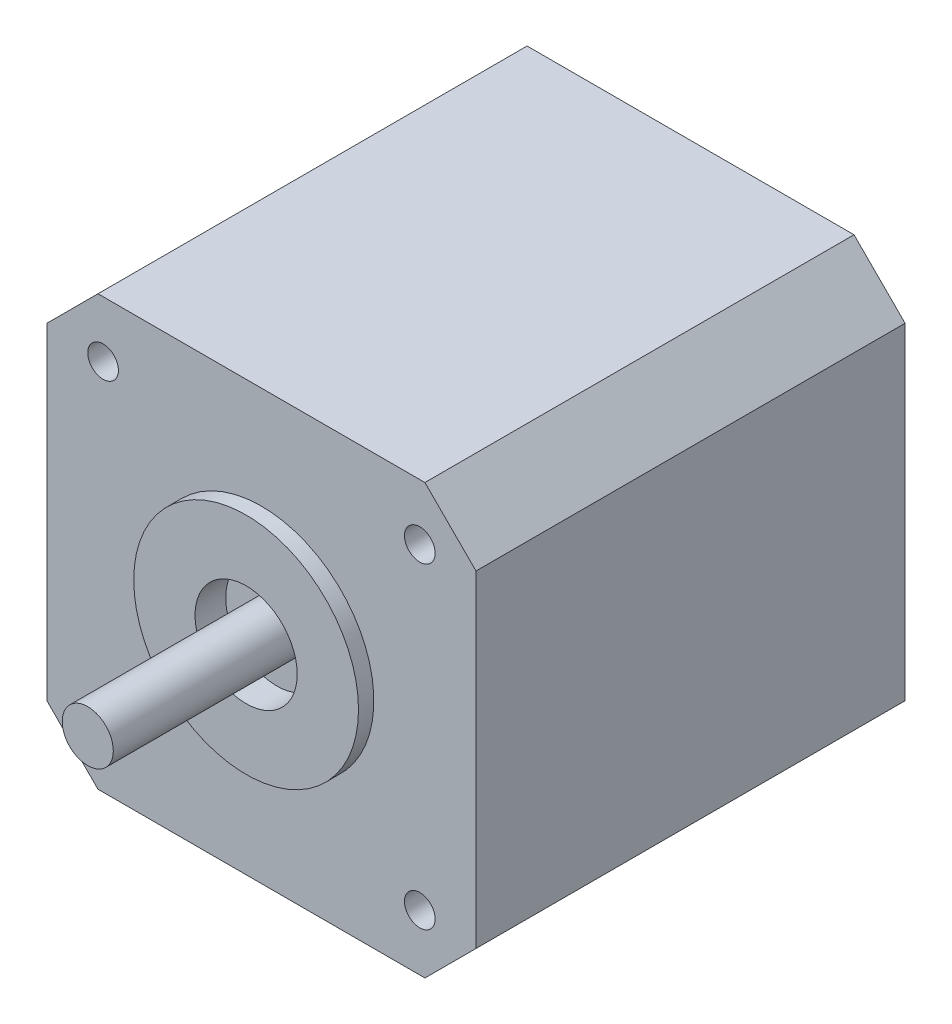
SolidWorks part; units mm, degrees
ref_plane "Front Plane" through (0, 0, 0) normal (0, 0, 1) x (1, 0, 0)
ref_plane "Top Plane" through (0, 0, 0) normal (0, 1, 0) x (1, 0, 0)
ref_plane "Right Plane" through (0, 0, 0) normal (1, 0, 0) x (0, 0, -1)
sketch "Sketch1" plane through (0, 0, 0) normal (0, 1, 0) x (1, 0, 0)
  line L1 (-21, -21) -> (21, -21)
  line L2 (-21, -21) -> (-21, 21)
  line L3 (-21, 21) -> (21, 21)
  line L4 (21, -21) -> (21, 21)
  line L5 (-21, -21) -> (21, 21) construction
  line L6 (-21, 21) -> (21, -21) construction
  point P0 (0, 0)
  dimension "D1" = 42
extrude "Boss-Extrude1" add sketch "Sketch1" along normal blind 42
sketch "Sketch2" plane through (0, 0, 21) normal (0, 0, 1) x (1, 0, 0)
  line L0 (0, 42) -> (0, 0) construction
  line L1 (-21, 42) -> (21, 42) construction
  line L2 (0, 21) -> (-21, 21) construction
  line L3 (-21, 42) -> (-21, 0) construction
  line L4 (21, 42) -> (21, 0) construction
  circle A0 centre (15.5, 36.5) radius 1.5
  circle A1 centre (-15.5, 36.5) radius 1.5
  circle A2 centre (15.5, 5.5) radius 1.5
  circle A3 centre (-15.5, 5.5) radius 1.5
  dimension "D1" = 3
  dimension "D2" = 5.5
  dimension "D3" = 5.5
extrude "Cut-Extrude1" cut sketch "Sketch2" against normal blind 42
sketch "Sketch3" plane through (0, 0, 21) normal (0, 0, 1) x (1, 0, 0)
  circle A0 centre (0, 21) radius 11
  dimension "D1" = 22
extrude "Boss-Extrude2" add sketch "Sketch3" along normal blind 1.5
sketch "Sketch4" plane through (0, 0, 22.5) normal (0, 0, 1) x (1, 0, 0)
  circle A0 centre (0, 21) radius 5
  dimension "D1" = 10
extrude "Cut-Extrude2" cut sketch "Sketch4" against normal blind 3
sketch "Sketch5" plane through (0, 0, 19.5) normal (0, 0, 1) x (1, 0, 0)
  circle A0 centre (0, 21) radius 2.5
  dimension "D1" = 5
extrude "Boss-Extrude3" add sketch "Sketch5" along normal blind 18.5
sketch "Sketch6" plane through (0, 0, -21) normal (0, 0, -1) x (-1, 0, 0)
  line L0 (0, 0) -> (0, 21) construction
  line L1 (-21, 0) -> (21, 0) construction
  line L2 (0, 21) -> (21, 21) construction
  line L3 (21, 42) -> (21, 0) construction
  circle A0 centre (15.5, 5.5) radius 3
  circle A1 centre (15.5, 36.5) radius 3
  circle A2 centre (-15.5, 5.5) radius 3
  circle A3 centre (-15.5, 36.5) radius 3
  dimension "D1" = 6
extrude "Cut-Extrude3" cut sketch "Sketch6" against normal blind 2
fillet "Chamfer1" radius 5 1 edges at (21, 42, 0) type face fillet profile chamfer first side face at (0, 42, 0) second side face at (21, 21, 0)
fillet "Chamfer2" radius 5 1 edges at (-21, 42, 0) type face fillet profile chamfer first side face at (-2.5, 42, 0) second side face at (-21, 21, 0)
fillet "Chamfer3" radius 5 1 edges at (-21, 0, 0) type face fillet profile chamfer first side face at (-21, 18.5, 0) second side face at (0, 0, 0)
fillet "Chamfer4" radius 5 1 edges at (21, 0, 0) type face fillet profile chamfer first side face at (21, 18.5, 0) second side face at (2.5, 0, 0)
sketch "Sketch7" plane through (0, 0, -21) normal (0, 0, -1) x (-1, 0, 0)
  line L0 (0, 0) -> (0, 42) construction
  line L1 (-16, 0) -> (16, 0) construction
  line L2 (-16, 42) -> (16, 42) construction
  line L3 (-21, 21) -> (21, 21) construction
  line L4 (-21, 37) -> (-21, 5) construction
  line L5 (21, 37) -> (21, 5) construction
  point P12 (0, 21)
